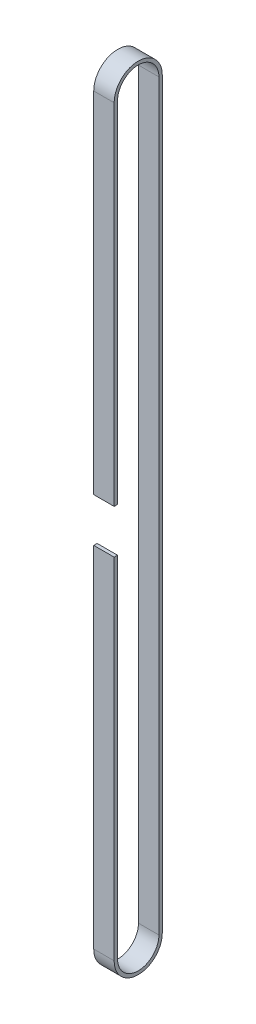
SolidWorks part; units mm, degrees
material "6063-T5"
ref_plane "Front Plane" through (0, 0, 0) normal (1, 0, 0) x (0, 1, 0)
ref_plane "Top Plane" through (0, 0, 0) normal (0, 0, 1) x (0, 1, 0)
ref_plane "Right Plane" through (0, 0, 0) normal (0, 1, 0) x (-1, 0, 0)
sketch "Sketch1" plane through (0, 0, 0) normal (1, 0, 0) x (0, 1, 0)
  line L0 (-110, 0) -> (110, 0) construction
  line L1 (-110, 6.125) -> (110, 6.125)
  line L2 (-110, -6.125) -> (110, -6.125)
  line L3 (-110, 7.125) -> (110, 7.125)
  line L4 (-110, -7.125) -> (110, -7.125)
  arc A0 (-110, 6.125) -> (-110, -6.125) centre (-110, 0) ccw
  arc A1 (110, -6.125) -> (110, 6.125) centre (110, 0) ccw
  arc A2 (110, -7.125) -> (110, 7.125) centre (110, 0) ccw
  arc A3 (-110, 7.125) -> (-110, -7.125) centre (-110, 0) ccw
  point P2 (0, 0)
  dimension "D2" = 6.125
  dimension "D1" = 220
  dimension "D3" = 1
extrude "Boss-Extrude1" add sketch "Sketch1" along normal blind 6.05
sketch "Sketch2" plane through (0, 0, 0) normal (1, 0, 0) x (0, 1, 0)
  line L0 (110, 7.125) -> (-110, 7.125) construction
  line L1 (-6.5, 7.125) -> (6.5, 7.125)
  line L2 (-6.5, 7.125) -> (-6.5, 6.125)
  line L3 (-6.5, 6.125) -> (6.5, 6.125)
  line L4 (6.5, 7.125) -> (6.5, 6.125)
  line L5 (110, 6.125) -> (-110, 6.125) construction
  line L6 (0, 6.125) -> (0, 0) construction
  dimension "D1" = 13
extrude "Cut-Extrude1" cut sketch "Sketch2" along normal up to surface (6.05 mm away) up to face at (6.05, 0, 0)
